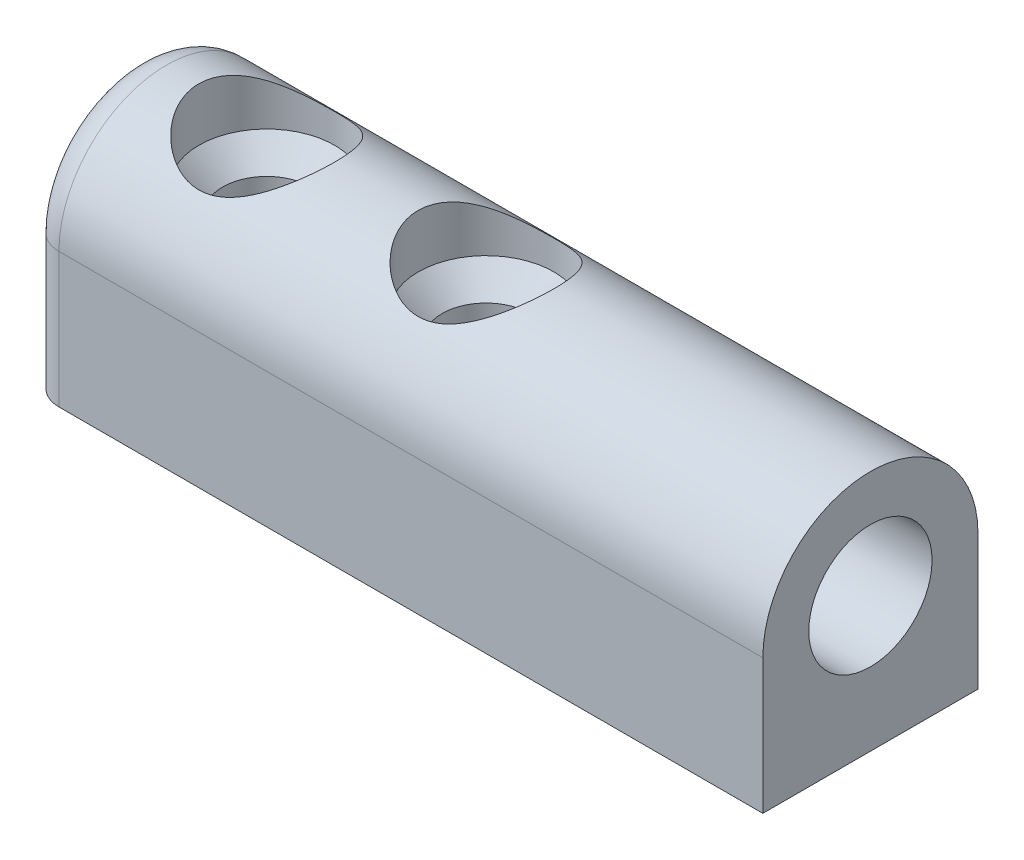
SolidWorks part; units mm, degrees
ref_plane "Plano frontal" through (0, 0, 0) normal (0, 0, 1) x (1, 0, 0)
ref_plane "Plano superior" through (0, 0, 0) normal (0, 1, 0) x (1, 0, 0)
ref_plane "Plano direito" through (0, 0, 0) normal (1, 0, 0) x (0, 0, -1)
sketch "Esboço1" plane through (0, 0, 0) normal (1, 0, 0) x (0, 0, -1)
  line L0 (0, 5.15) -> (0, -6.4502) construction
  line L1 (5.15, -6.4502) -> (-5.15, -6.4502)
  line L2 (-5.15, -6.4502) -> (-5.15, 0)
  line L3 (5.15, -6.4502) -> (5.15, 0)
  circle A0 centre (0, 0) radius 2.95
  arc A1 (5.15, 0) -> (-5.15, 0) centre (0, 0) ccw
  circle A2 centre (0, 0) radius 5.15 construction
  dimension "D1" = 5.9
  dimension "D3" = 11.6002
  dimension "D2" = 2.2
extrude "Ressalto-extrusão1" add sketch "Esboço1" along normal mid plane 35.2
sketch "Esboço2" plane through (-17.6, 0, 0) normal (-1, 0, 0) x (0, 0, 1)
  line L3 (-5.15, 0) -> (-5.15, -6.4502)
  line L4 (-5.15, -6.4502) -> (5.15, -6.4502)
  line L5 (5.15, -6.4502) -> (5.15, 0)
  line L6 (-5.15, 0) -> (-5.15, -6.4502)
  line L7 (-5.15, -6.4502) -> (5.15, -6.4502)
  line L8 (5.15, -6.4502) -> (5.15, 0)
  arc A1 (5.15, 0) -> (-5.15, 0) centre (0, 0) ccw
  arc A2 (5.15, 0) -> (-5.15, 0) centre (0, 0) ccw
  dimension "D1" = 0
extrude "Ressalto-extrusão2" add sketch "Esboço2" against normal blind 20.5
fillet "Filete1" radius 1.5 3 edges at (-17.6, -3.2251, -5.15) (-17.6, -3.2251, 5.15) (-17.6, 5.15, 0)
sketch "Esboço3" plane through (0, -6.4502, 0) normal (0, -1, 0) x (1, 0, 0)
  line L0 (-17.6, 0) -> (-11.3, 0) construction
  line L1 (-17.6, 3.65) -> (-17.6, -3.65) construction
  circle A0 centre (-11.3, 0) radius 3.25
  circle A1 centre (-0.8, 0) radius 3.25
  dimension "D1" = 6.5
  dimension "D2" = 2
extrude "Corte-extrusão1" cut sketch "Esboço3" against normal through all
sketch "Esboço5" plane through (0, -6.4502, 0) normal (0, -1, 0) x (1, 0, 0)
  circle A0 centre (-11.3, 0) radius 2.1
  circle A1 centre (-0.8, 0) radius 2.1
  circle A2 centre (-0.8, 0) radius 3.25 construction
  circle A3 centre (-0.8, 0) radius 3.25
  circle A4 centre (-11.3, 0) radius 3.25 construction
  circle A5 centre (-11.3, 0) radius 3.25
  dimension "D1" = 4.2
extrude "Ressalto-extrusão3" add sketch "Esboço5" against normal blind 9.1
chamfer "Chanfro1" distance 1.2 angle 45 2 edges at (-11.3, 2.6498, -2.1) (-0.8, 2.6498, -2.1)
